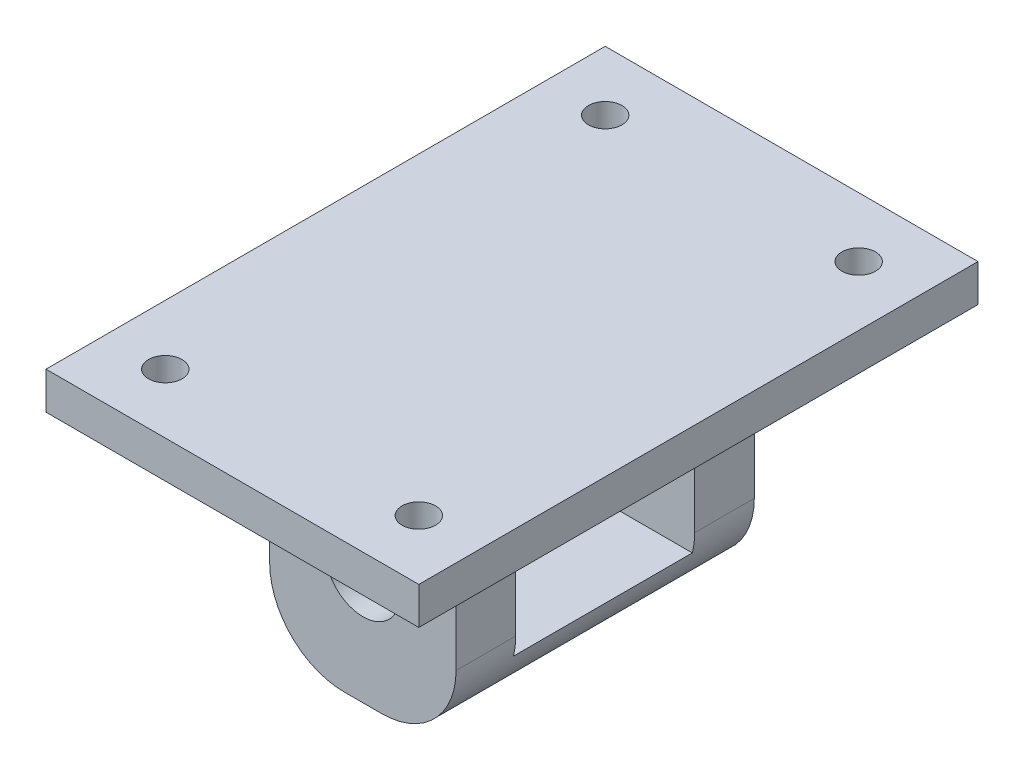
SolidWorks part; units mm, degrees
ref_plane "Front Plane" through (0, 0, 0) normal (0, 0, 1) x (1, 0, 0)
ref_plane "Top Plane" through (0, 0, 0) normal (0, 1, 0) x (1, 0, 0)
ref_plane "Right Plane" through (0, 0, 0) normal (1, 0, 0) x (0, 0, -1)
sketch "Sketch1" plane through (0, 0, 0) normal (0, 0, 1) x (1, 0, 0)
  line L1 (12.5, -15) -> (-12.5, -15)
  line L2 (12.5, -15) -> (12.5, 15)
  line L3 (12.5, 15) -> (-12.5, 15)
  line L4 (-12.5, -15) -> (-12.5, 15)
  line L5 (12.5, -15) -> (-12.5, 15) construction
  line L6 (12.5, 15) -> (-12.5, -15) construction
  point P0 (0, 0)
  dimension "D1" = 15
  dimension "D2" = 25
extrude "Boss-Extrude1" add sketch "Sketch1" along normal mid plane 40
sketch "Sketch2" plane through (0, 0, 0) normal (0, 0, 1) x (1, 0, 0)
  line L0 (0, 7.5) -> (21.3989, 7.5)
  line L3 (21.3989, -7.5) -> (0, -7.5)
  line L4 (21.3989, 7.5) -> (21.3989, -7.5)
  arc A0 (0, 7.5) -> (0, -7.5) centre (0, 0) ccw
  dimension "D1" = 15
extrude "Cut-Extrude1" cut sketch "Sketch2" against normal blind 12 and the other way blind 12
sketch "Sketch3" plane through (0, 0, 20) normal (0, 0, 1) x (1, 0, 0)
  circle A0 centre (0, 0) radius 5
  dimension "D1" = 10
extrude "Cut-Extrude2" cut sketch "Sketch3" against normal through all
sketch "Sketch4" plane through (0, 15, 0) normal (0, 1, 0) x (1, 0, 0)
  line L1 (25, -37.5) -> (-25, -37.5)
  line L2 (25, -37.5) -> (25, 37.5)
  line L3 (25, 37.5) -> (-25, 37.5)
  line L4 (-25, -37.5) -> (-25, 37.5)
  line L5 (25, -37.5) -> (-25, 37.5) construction
  line L6 (25, 37.5) -> (-25, -37.5) construction
  point P0 (0, 0)
  dimension "D1" = 50
  dimension "D2" = 75
extrude "Boss-Extrude2" add sketch "Sketch4" along normal blind 5
fillet "Fillet1" radius 10 2 edges at (-12.5, -15, 0) (12.5, -15, 0)
hole_wizard "M4 Clearance Hole1" positions "Sketch6" profile "Sketch7" hole size "M4" standard "ISO" end condition through all
sketch "Sketch6" plane through (0, 15, 0) normal (0, -1, 0) x (-1, 0, 0)
  line L0 (-25, -37.5) -> (-25, 37.5) construction
  line L1 (-25, 37.5) -> (25, 37.5) construction
  line L2 (25, 37.5) -> (25, -37.5) construction
  line L3 (25, -37.5) -> (-25, -37.5) construction
  point P0 (-17, 29.5)
  point P2 (17, 29.5)
  point P4 (17, -29.5)
  point P6 (-17, -29.5)
  point P15 (-7.9831, 35.4309)
  dimension "D1" = 8
  dimension "D2" = 8
  dimension "D3" = 8
  dimension "D4" = 8
  dimension "D5" = 8
  dimension "D6" = 8
  dimension "D7" = 8
  dimension "D8" = 8
sketch "Sketch7" plane through (17, 15, -29.5) normal (1, 0, 0) x (0, 0, -1)
  line L0 (0, 0) -> (0, 5)
  line L1 (0, 5) -> (2.25, 5)
  line L2 (2.25, 5) -> (2.25, 0.025)
  line L3 (2.25, 0.025) -> (2.275, 0)
  line L5 (2.275, 0) -> (0, 0)
  line L6 (-2.25, 0.025) -> (-2.275, 0) construction
  line L11 (0, -6.35) -> (0, 107.95) construction
  dimension "Thru Hole Dia." = 4.5
  dimension "Thru Hole Depth" = 5
  dimension "Near C'Sink Dia." = 4.55
  dimension "Near C'Sink Angle" = 90
